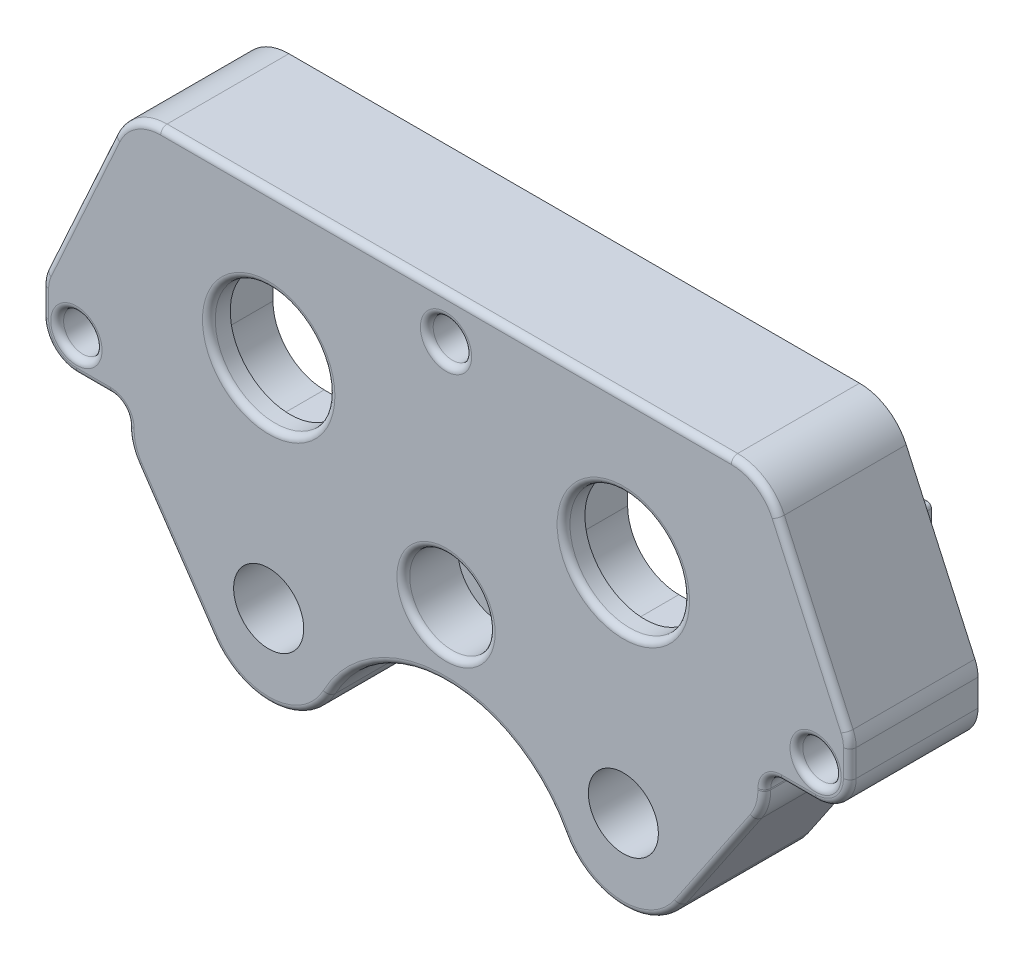
SolidWorks part; units mm, degrees
ref_plane "Front Plane" through (0, 0, 0) normal (0, 0, 1) x (1, 0, 0)
ref_plane "Top Plane" through (0, 0, 0) normal (0, 1, 0) x (1, 0, 0)
ref_plane "Right Plane" through (0, 0, 0) normal (1, 0, 0) x (0, 0, -1)
sketch "Sketch1" plane through (0, 0, 0) normal (0, 0, 1) x (1, 0, 0)
  line L0 (56, 15) -> (27, 15)
  line L1 (14.5, 15) -> (-14.5, 15)
  line L2 (14.5, 15) -> (14.5, -15)
  line L3 (14.5, -15) -> (-14.5, -15)
  line L4 (-14.5, 15) -> (-14.5, -15)
  line L5 (14.5, 15) -> (-14.5, -15) construction
  line L6 (14.5, -15) -> (-14.5, 15) construction
  line L7 (-16.75, -42) -> (16.75, -42)
  line L8 (-16.75, -42) -> (-16.75, 16)
  line L9 (-16.75, 16) -> (16.75, 16)
  line L10 (16.75, -42) -> (16.75, 16)
  line L11 (56, 15) -> (56, -15)
  line L12 (56, -15) -> (27, -15)
  line L13 (27, 15) -> (27, -15)
  line L14 (56, 15) -> (27, -15) construction
  line L15 (56, -15) -> (27, 15) construction
  line L16 (24.75, -42) -> (58.25, -42)
  line L17 (24.75, -42) -> (24.75, 16)
  line L18 (24.75, 16) -> (58.25, 16)
  line L19 (58.25, -42) -> (58.25, 16)
  circle A0 centre (0, 0) radius 19.05 construction
  circle A1 centre (41.5, 0) radius 19.05 construction
  circle A2 centre (20.75, -14.6491) radius 6.35 construction
  circle A3 centre (20.75, -14.6491) radius 41.275 construction
  circle A4 centre (0, 0) radius 7
  circle A5 centre (41.5, 0) radius 7
  circle A6 centre (0, -25.4) radius 4.3
  circle A7 centre (0, -27.1) radius 6.75
  circle A8 centre (41.5, -27.1) radius 6.75
  circle A9 centre (41.5, -25.4) radius 4.3
  point P0 (0, 0)
  point P10 (41.5, 0)
  point P11 (0, -42)
  point P22 (41.5, -42)
  dimension "D6" = 38.1
  dimension "D12" = 38.1
  dimension "D13" = 12.7
  dimension "D15" = 82.55
  dimension "D20" = 14
  dimension "D21" = 14
  dimension "D16" = 8.6
  dimension "D18" = 13.5
  dimension "D1" = 33.5
  dimension "D2" = 29
  dimension "D3" = 30
  dimension "D4" = 16
  dimension "D5" = 58
  dimension "D7" = 33.5
  dimension "D8" = 29
  dimension "D9" = 30
  dimension "D10" = 16
  dimension "D11" = 58
  dimension "D14" = 8
  dimension "D17" = 10.4
  dimension "D19" = 1.7
sketch "Sketch5" plane through (0, 0, 0) normal (0, 0, 1) x (1, 0, 0)
  line L0 (56, 15) -> (27, -15) construction
  line L1 (14.5, 15) -> (-14.5, 15) construction
  line L2 (-16.5, 17) -> (58, 17)
  line L3 (-16.5, 17) -> (-16.5, -35.1)
  line L4 (-16.5, -35.1) -> (58, -35.1)
  line L5 (58, 17) -> (58, -35.1)
  line L6 (-14.5, 15) -> (-14.5, -15) construction
  line L7 (56, 15) -> (56, -15) construction
  line L8 (14.5, -15) -> (-14.5, -15) construction
  line L9 (-16.5, -17) -> (-6.6243, -31.5853)
  line L10 (56, -15) -> (27, -15) construction
  line L11 (58, -17) -> (48.1243, -31.5853)
  line L12 (-26.5, -5) -> (-16.5, 17)
  line L13 (-16.5, -5) -> (-26.5, -5)
  line L14 (-16.5, -5) -> (-16.5, -13)
  line L15 (-16.5, -13) -> (-26.5, -13)
  line L16 (-26.5, -5) -> (-26.5, -13)
  line L17 (58, -5) -> (68, -5)
  line L18 (58, -5) -> (58, -13)
  line L19 (58, -13) -> (68, -13)
  line L20 (68, -5) -> (68, -13)
  line L21 (58, 17) -> (68, -5)
  circle A0 centre (0, 0) radius 7
  circle A1 centre (41.5, 0) radius 7
  circle A2 centre (20.75, -14.6491) radius 5
  circle A3 centre (0, -25.4) radius 4.1
  circle A4 centre (41.5, -25.4) radius 4.1
  circle A5 centre (41.5, -27.1) radius 6.75
  circle A6 centre (0, -27.1) radius 6.75
  circle A7 centre (0, -27.1) radius 8
  circle A8 centre (41.5, -27.1) radius 8
  circle A9 centre (-22.5, -9) radius 2.25
  circle A10 centre (20.75, 12) radius 2.25
  circle A11 centre (64, -9) radius 2.25
  circle A12 centre (20.75, -38.1651) radius 15.5159
  point P32 (-16.5, -17)
  point P39 (58, -17)
  point P58 (20.75, -22.6491)
  dimension "D1" = 10
  dimension "D2" = 14
  dimension "D3" = 14
  dimension "D4" = 8.2
  dimension "D5" = 8
  dimension "D6" = 13.5
  dimension "D7" = 13.5
  dimension "D18" = 4.5
  dimension "D22" = 4.5
  dimension "D26" = 4.5
  dimension "D8" = 8
  dimension "D9" = 2
  dimension "D10" = 2
  dimension "D11" = 2
  dimension "D12" = 2
  dimension "D13" = 2
  dimension "D14" = 8
  dimension "D15" = 10
  dimension "D16" = 9
  dimension "D17" = 10
  dimension "D19" = 8
  dimension "D20" = 6
  dimension "D21" = 4
  dimension "D23" = 21
  dimension "D24" = 4
  dimension "D25" = 6
extrude "Boss-Extrude5" add sketch "Sketch5" against normal blind 15 contours A8 A5 | A7 A6 | A6 A3 | A5 A4 | A8 L11 L5 L2 L3 L9 A7 L4 A10 A2 A1 A0 | L13 L16 L15 L3 A9 | L20 L17 L5 L19 A11 | L13 L3 L12 | L21 L5 L17 region at (20.75, -3.0591, 0) region at (-19.8333, 2.3333, 0) region at (61.3333, 2.3333, 0) region at (-16.6281, -9, 0) region at (63, -5.1281, 0) region at (-2.2794, -19.668, 0) region at (45.1434, -33.967, 0) region at (34.9409, -27.1, 0) region at (-6.5591, -27.1, 0)
extrude "Cut-Extrude1" cut sketch "Sketch1" along normal blind 12.5 from surface contours L1 L4 L3 L2 A4 | L0 L13 L12 L11 A5 region at (55.5827, 0, 0) region at (14.0827, 0, 0) starting at face at (20.75, -13.3152, -15)
extrude "Cut-Extrude2" cut sketch "Sketch5<3>" along normal blind 2 from surface contours A5 A4 | A6 A3 region at (34.9409, -27.1, 0) region at (-6.5591, -27.1, 0) starting at face at (0, 0, -15)
sketch "Sketch5<3>" plane through (0, 0, 0) normal (0, 0, 1) x (1, 0, 0) same geometry as "Sketch5"
fillet "Fillet1" radius 6 8 edges at (56, 15, -8.75) (56, -15, -8.75) (27, -15, -8.75) (27, 15, -8.75) (14.5, -15, -8.75) (-14.5, -15, -8.75) (-14.5, 15, -8.75) (14.5, 15, -8.75)
fillet "Fillet2" radius 4 4 edges at (-26.5, -5, -7.5) (-26.5, -13, -7.5) (68, -5, -7.5) (68, -13, -7.5)
fillet "Fillet3" radius 6 4 edges at (-16.5, -17, -7.5) (58, -17, -7.5) (-16.5, 17, -7.5) (58, 17, -7.5)
fillet "Fillet4" radius 2 2 edges at (-16.5, -13, -7.5) (58, -13, -7.5)
extrude "Boss-Extrude6" add sketch "Sketch5<4>" along normal blind 8.65 from surface contours A2 region at (20.75, -14.6491, 0) starting at face at (6.75, -27.1, -15)
sketch "Sketch5<4>" plane through (0, 0, 0) normal (0, 0, 1) x (1, 0, 0) same geometry as "Sketch5"
sketch "Sketch6" plane through (0, 0, 0) normal (0, 0, 1) x (1, 0, 0)
  line L1 (-18.8338, -9) -> (-20.6669, -5.825)
  line L2 (-20.6669, -5.825) -> (-24.3331, -5.825)
  line L3 (-24.3331, -5.825) -> (-26.1662, -9)
  line L4 (-26.1662, -9) -> (-24.3331, -12.175)
  line L5 (-24.3331, -12.175) -> (-20.6669, -12.175)
  line L6 (-20.6669, -12.175) -> (-18.8338, -9)
  line L7 (24.287, 11.0352) -> (23.354, 14.5807)
  line L8 (23.354, 14.5807) -> (19.817, 15.5455)
  line L9 (19.817, 15.5455) -> (17.213, 12.9648)
  line L10 (17.213, 12.9648) -> (18.146, 9.4193)
  line L11 (18.146, 9.4193) -> (21.683, 8.4545)
  line L12 (21.683, 8.4545) -> (24.287, 11.0352)
  line L13 (60.3338, -9) -> (62.1669, -12.175)
  line L14 (62.1669, -12.175) -> (65.8331, -12.175)
  line L15 (65.8331, -12.175) -> (67.6662, -9)
  line L16 (67.6662, -9) -> (65.8331, -5.825)
  line L17 (65.8331, -5.825) -> (62.1669, -5.825)
  line L18 (62.1669, -5.825) -> (60.3338, -9)
  circle A0 centre (-22.5, -9) radius 3.175 construction
  circle A1 centre (20.75, 12) radius 3.175 construction
  circle A2 centre (64, -9) radius 3.175 construction
  dimension "D1" = 6.35
  dimension "D2" = 6.35
  dimension "D3" = 6.35
fillet "Fillet5" radius 0.75 30 edges at (-15.8848, 16.0446, 0) (-22.1201, 4.6358, 0) (-26.4093, -5.0196, 0) (-26.5, -7.4332, 0) (-25.3284, -11.8284, 0) (-20.5, -13, 0) (-17.0858, -13.5858, 0) (-16.5, -15.0799, 0) (-16.2363, -16.9191, 0) (-11.0463, -25.0545, 0) (0.421, -35.0889, 0) (20.75, -22.6491, 0) (41.079, -35.0889, 0) (52.5463, -25.0545, 0) (57.7363, -16.9191, 0) (58, -15.0799, 0) (58.5858, -13.5858, 0) (62, -13, 0) (66.8284, -11.8284, 0) (68, -7.4332, 0) (67.9093, -5.0196, 0) (63.6201, 4.6358, 0) (57.3848, 16.0446, 0) (66.25, -9, 0) (48.5, 0, 0) (25.75, -14.6491, 0) (23, 12, 0) (7, 0, 0) (-20.25, -9, 0) (20.75, 17, 0)
sketch "Sketch7" plane through (0, 0, -15) normal (0, 0, -1) x (-1, 0, 0)
  line L1 (-24.9, 7) -> (-16.6, 7)
  line L2 (-24.9, 7) -> (-24.9, -3)
  line L3 (-24.9, -3) -> (-16.6, -3)
  line L4 (-16.6, 7) -> (-16.6, -3)
  line L5 (-60.55, 7) -> (-58.55, 7)
  line L6 (-60.55, 7) -> (-60.55, -3)
  line L7 (-60.55, -3) -> (-58.55, -3)
  line L8 (-58.55, 7) -> (-58.55, -3)
  line L9 (17.05, 7) -> (19.05, 7)
  line L10 (17.05, 7) -> (17.05, -3)
  line L11 (17.05, -3) -> (19.05, -3)
  line L12 (19.05, 7) -> (19.05, -3)
  circle A0 centre (-20.75, 12) radius 2.25 construction
  circle A1 centre (-64, -9) radius 2.25 construction
  circle A2 centre (22.5, -9) radius 2.25 construction
  dimension "D1" = 4.15
  dimension "D2" = 5.45
  dimension "D3" = 4.15
  dimension "D4" = 10
  dimension "D5" = 5
  dimension "D6" = 10
  dimension "D7" = 2
  dimension "D8" = 5.45
extrude "Boss-Extrude7" add sketch "Sketch7" along normal blind 2
fillet "Fillet6" radius 0.5 25 edges at (-19.05, 2, -15) (20.75, -3, -15) (59.55, -3, -15) (-18.05, 7, -15) (-18.05, -3, -15) (24.9, 2, -15) (16.6, 2, -15) (58.55, 2, -15) (60.55, 2, -15) (-17.05, 7, -16) (-17.05, 2, -17) (-17.05, -3, -16) (-17.05, 2, -15) (-19.05, 7, -16) (-19.05, -3, -16) (16.6, -3, -16) (24.9, -3, -16) (24.9, 7, -16) (16.6, 7, -16) (20.75, 7, -15) (59.55, 7, -15) (60.55, 7, -16) (58.55, 7, -16) (58.55, -3, -16) (60.55, -3, -16)
